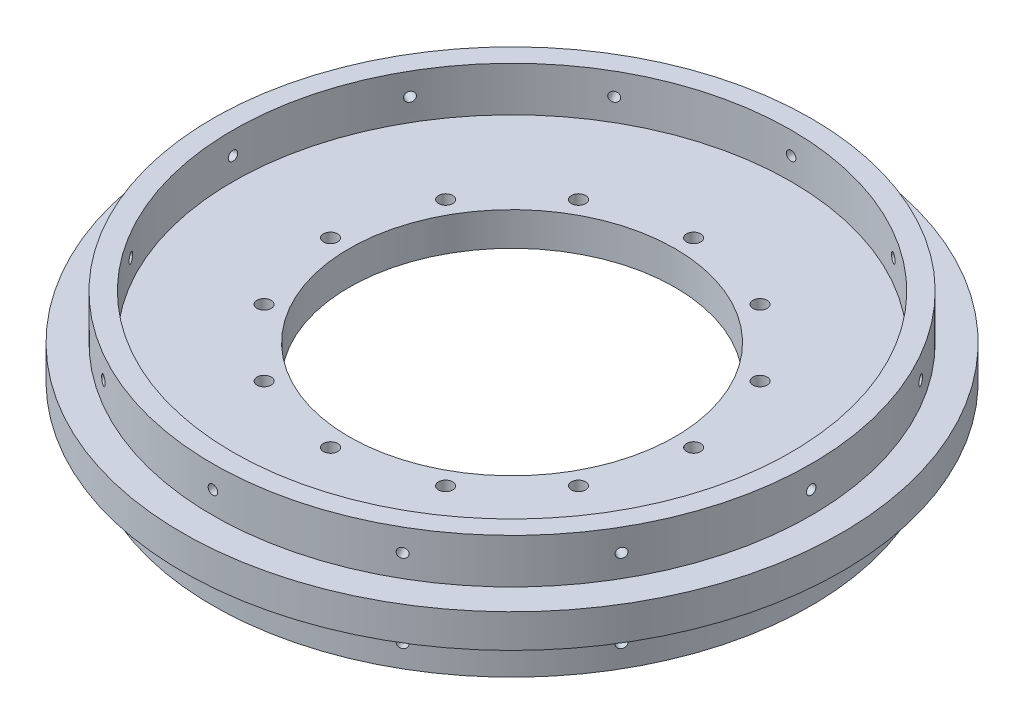
SolidWorks part; units mm, degrees
material "6061-T6 (SS)"
ref_plane "Front Plane" through (0, 0, 0) normal (0, 0, 1) x (1, 0, 0)
ref_plane "Top Plane" through (0, 0, 0) normal (0, 1, 0) x (1, 0, 0)
ref_plane "Right Plane" through (0, 0, 0) normal (1, 0, 0) x (0, 0, -1)
sketch "Sketch1" plane through (0, 0, 0) normal (0, 1, 0) x (1, 0, 0)
  line L5 (0, 0) -> (127.635, 0)
  line L6 (0, 0) -> (0, 127.635)
  line L7 (0, 127.635) -> (127.635, 127.635)
  line L8 (127.635, 0) -> (127.635, 127.635)
  dimension "D1" = 127.635
  dimension "D2" = 127.635
extrude "Boss-Extrude1" add sketch "Sketch1" along normal blind 9.525 contours L5 L8 L7 L6
sketch "Sketch12" plane through (0, 0, 0) normal (0, -1, 0) x (1, 0, 0)
  line L0 (63.8175, 0) -> (63.8175, -127.635) construction
  line L1 (0, 0) -> (127.635, 0) construction
  line L2 (0, -127.635) -> (127.635, -127.635) construction
  line L3 (0, -63.8175) -> (127.635, -63.8175) construction
  line L4 (0, 0) -> (0, -127.635) construction
  line L5 (127.635, 0) -> (127.635, -127.635) construction
  circle A0 centre (63.8175, -63.8175) radius 93.726
  dimension "D1" = 187.452
extrude "Boss-Extrude2" add sketch "Sketch12" against normal up to surface (9.525 mm away) contours A0 up to face at (63.8175, 9.525, -63.8175)
sketch "Sketch5" plane through (0, 9.525, 0) normal (0, 1, 0) x (1, 0, 0)
  circle A0 centre (63.8175, 63.8175) radius 46.355
  circle A3 centre (63.8175, 63.8175) radius 93.726 construction
  dimension "D1" = 92.71
extrude "Cut-Extrude1" cut sketch "Sketch5" against normal blind 9.525
sketch "Sketch11" plane through (0, 9.525, 0) normal (0, 1, 0) x (1, 0, 0)
  line L0 (63.8175, 63.8175) -> (63.8175, 115.443) construction
  circle A0 centre (63.8175, 115.443) radius 2.0193
  dimension "D2" = 4.0386
  dimension "D1" = 51.6255
extrude "Cut-Extrude3" cut sketch "Sketch11" against normal through all contours A0
pattern_circular "CirPattern1" count 12 over 360 about axis through (63.8175, 9.525, -63.8175) along (0, 1, 0) of "Cut-Extrude3"
sketch "Sketch14" plane through (0, 9.525, 0) normal (0, -1, 0) x (1, 0, 0)
  line L0 (63.8175, -63.8175) -> (147.6375, -63.8175) construction
  line L1 (0, -5.2388) -> (0, 5.2388) construction
  line L2 (147.6375, -63.8175) -> (152.7175, -63.8175)
  line L3 (136.3808, -105.7742) -> (140.8401, -108.2104)
  circle A0 centre (63.8175, -63.8175) radius 46.355 construction
  arc A2 (147.6375, -63.8175) -> (136.3808, -105.7742) centre (63.8175, -63.8175) cw
  arc A3 (152.7175, -63.8175) -> (140.8401, -108.2104) centre (63.8175, -63.8175) cw
  point P0 (63.8175, -63.8175)
  dimension "D1" = 83.82
  dimension "D2" = 88.9
  dimension "D3" = 46.482
  dimension "D4" = 43.942
ref_plane "Support mirror reference plane" through (0, 4.7625, 0) normal (0, 1, 0) x (1, 0, 0)
sketch "Sketch25" plane through (0, 9.525, 0) normal (0, -1, 0) x (1, 0, 0)
  line L0 (63.8175, -63.8175) -> (123.0872, -4.5478) construction
  line L2 (123.0872, -4.5478) -> (126.6793, -0.9557)
  line L3 (144.7953, -42.1754) -> (149.6712, -40.7448)
  line L5 (63.8175, -63.8175) -> (147.6375, -63.8175) construction
  arc A2 (123.0872, -4.5478) -> (144.7953, -42.1754) centre (63.8175, -63.8175) cw
  arc A3 (126.6793, -0.9557) -> (149.6712, -40.7448) centre (63.8175, -63.8175) cw
  point P0 (63.8175, -63.8175)
  dimension "D1" = 83.82
  dimension "D2" = 88.9
  dimension "D3" = 46.482
  dimension "D4" = 43.942
  dimension "D5" = 45
sketch "Sketch30" plane through (0, 0, 0) normal (0, -1, 0) x (1, 0, 0)
  circle A0 centre (63.8175, -63.8175) radius 85.09
  circle A1 centre (63.8175, -63.8175) radius 79.375
  dimension "D1" = 170.18
  dimension "D2" = 158.75
extrude "Boss-Extrude3" add sketch "Sketch30" along normal blind 12.7
mirror "Mirror1" about plane through (0, 4.7625, 0) normal (0, 1, 0) of "Boss-Extrude3"
sketch "Sketch31" plane through (0, 0, 0) normal (0, -1, 0) x (-1, 0, 0)
  line L0 (-63.8175, -52.481) -> (-63.8175, 177.7216) construction
ref_plane "Plane1" through (0, 0, -148.9075) normal (0, 0, -1) x (-1, 0, 0)
ref_plane "Plane2" through (63.8175, 0, 0) normal (-1, 0, 0) x (0, 0, -1)
sketch "Sketch32" plane through (0, 0, -148.9075) normal (0, 0, -1) x (-1, 0, 0)
  line L4 (-63.8175, -87.3125) -> (-63.8175, 87.3125) construction
  line L5 (-148.9075, 0) -> (21.2725, 0) construction
  line L6 (21.2725, 9.525) -> (-148.9075, 9.525) construction
  circle A0 centre (-63.8175, -6.35) radius 1.3526
  circle A1 centre (-63.8175, 15.875) radius 1.3525
  dimension "D1" = 2.7051
  dimension "D2" = 2.7051
  dimension "D3" = 6.35
  dimension "D4" = 6.35
extrude "Cut-Extrude4" cut sketch "Sketch32" against normal blind 15.24
pattern_circular "CirPattern2" count 12 over 360 about axis through (63.8175, -12.7, -63.8175) along (0, 1, 0) of "Cut-Extrude4"
